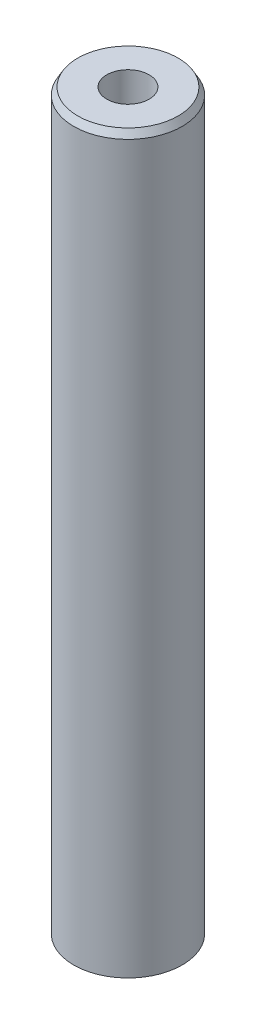
SolidWorks part; units mm, degrees
ref_plane "Front Plane" through (0, 0, 0) normal (0, 0, 1) x (1, 0, 0)
ref_plane "Top Plane" through (0, 0, 0) normal (0, 1, 0) x (1, 0, 0)
ref_plane "Right Plane" through (0, 0, 0) normal (1, 0, 0) x (0, 0, -1)
sketch "Sketch1" plane through (0, 0, 0) normal (0, 1, 0) x (1, 0, 0)
  circle A0 centre (0, 0) radius 35
  dimension "SHAFT_OD" = 70
extrude "Boss-Extrude1" add sketch "Sketch1" along normal blind 475.6515
sketch "Sketch2" plane through (0, 0, 0) normal (0, 1, 0) x (1, 0, 0)
  circle A0 centre (0, 0) radius 13.6741
  dimension "BORE_D" = 27.3482
extrude "Cut-Extrude1" cut sketch "Sketch2" along normal through all
chamfer "Chamfer1" distance 4.5285 angle 30 2 edges at (0, 475.6515, 35) (0, 0, 35) first distance on face at (0, 475.6515, 35) first distance on face at (0, 0, 13.6741)
